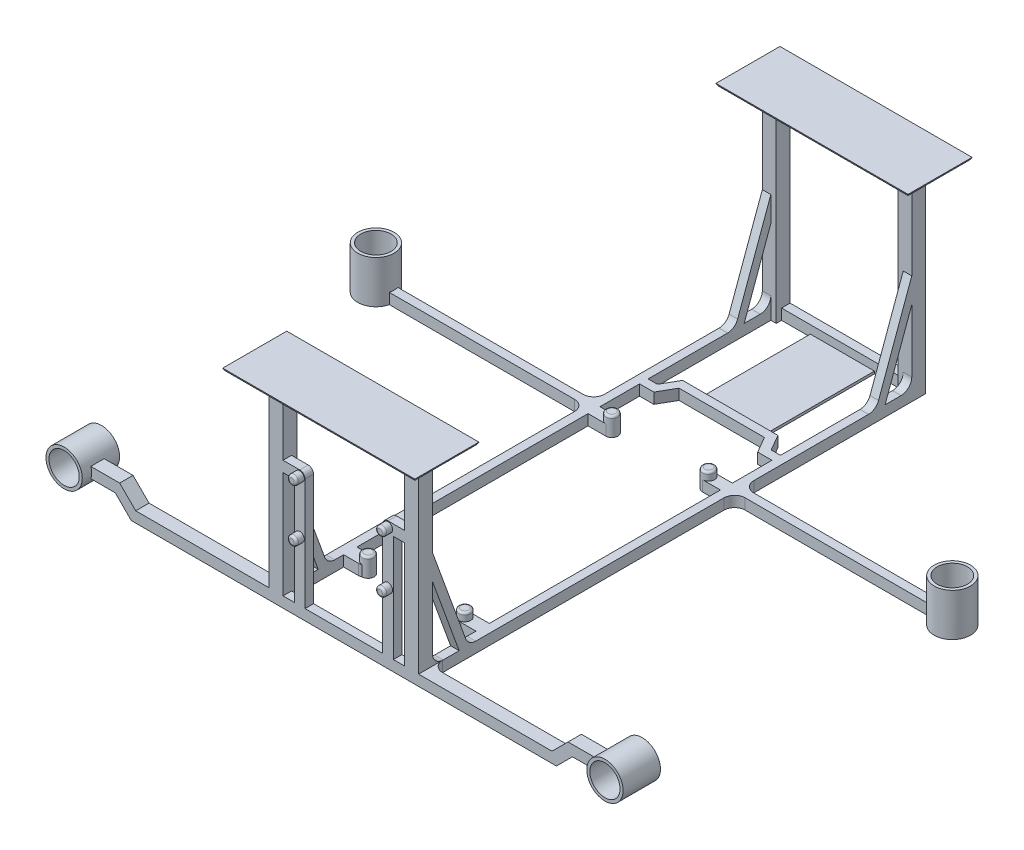
SolidWorks part; units mm, degrees
ref_plane "Front Plane" through (0, 0, 0) normal (0, 0, 1) x (1, 0, 0)
ref_plane "Top Plane" through (0, 0, 0) normal (0, 1, 0) x (1, 0, 0)
ref_plane "Right Plane" through (0, 0, 0) normal (1, 0, 0) x (0, 0, -1)
sketch "Sketch1" plane through (0, 0, 0) normal (0, 1, 0) x (1, 0, 0)
  line L6 (17.78, -60.325) -> (-17.78, -60.325)
  line L14 (17.78, -60.325) -> (17.78, 60.325)
  line L17 (17.78, 60.325) -> (-17.78, 60.325)
  line L19 (-17.78, -60.325) -> (-17.78, 60.325)
  line L20 (17.78, -60.325) -> (-17.78, 60.325) construction
  line L21 (17.78, 60.325) -> (-17.78, -60.325) construction
  line L22 (-15.748, -57.023) -> (-15.748, -44.6405)
  line L23 (14.478, -58.293) -> (-14.478, -58.293)
  line L24 (15.748, -57.023) -> (15.748, -44.6405)
  line L33 (-11.5, -43.053) -> (11.5, -43.053) construction
  line L34 (-11.5, -43.053) -> (-11.5, 14.947) construction
  line L35 (-11.5, 14.947) -> (11.5, 14.947) construction
  line L36 (11.5, -43.053) -> (11.5, 14.947) construction
  line L37 (0, -43.053) -> (0, -58.293) construction
  line L39 (-15.748, 25.781) -> (-12.3597, 25.781)
  line L43 (-15.748, -41.4655) -> (-11.5, -41.4655)
  line L44 (-15.748, -44.6405) -> (-11.5, -44.6405)
  line L45 (-11.5, -41.4655) -> (-11.5, -44.6405)
  line L46 (15.748, -41.4655) -> (11.5, -41.4655)
  line L47 (11.5, -41.4655) -> (11.5, -44.6405)
  line L48 (11.5, -44.6405) -> (15.748, -44.6405)
  line L52 (-15.748, -41.4655) -> (-15.748, 13.5246)
  line L53 (-15.748, -58.293) -> (-15.748, 58.293) construction
  line L54 (15.748, -41.4655) -> (15.748, 13.5246)
  line L55 (15.748, -58.293) -> (15.748, 58.293) construction
  line L58 (-15.748, 27.813) -> (-13.5329, 27.813)
  line L68 (1.016, 33.7192) -> (-1.016, 33.7192) construction
  line L70 (1.016, 33.7192) -> (-1.016, 33.7192) construction
  line L73 (0, 33.7192) -> (0, 29.591) construction
  line L75 (14.478, 58.293) -> (10.668, 58.293)
  line L76 (15.748, 58.293) -> (-15.748, 58.293) construction
  line L82 (-15.748, 27.813) -> (-15.748, 57.023)
  line L83 (15.748, 27.813) -> (15.748, 57.023)
  line L87 (-15.748, 57.023) -> (-14.478, 57.023)
  line L88 (-14.478, 58.293) -> (-14.478, 57.023)
  line L92 (15.748, 57.023) -> (14.478, 57.023)
  line L93 (14.478, 58.293) -> (14.478, 57.023)
  line L97 (-15.748, -57.023) -> (-14.478, -57.023)
  line L98 (-14.478, -58.293) -> (-14.478, -57.023)
  line L99 (15.748, -58.293) -> (-15.748, -58.293) construction
  line L102 (15.748, -57.023) -> (14.478, -57.023)
  line L103 (14.478, -58.293) -> (14.478, -57.023)
  line L104 (-12.3597, 25.781) -> (-10.16, 29.591)
  line L105 (-10.16, 29.591) -> (10.16, 29.591)
  line L106 (10.16, 29.591) -> (12.3597, 25.781)
  line L108 (-13.5329, 27.813) -> (-10.668, 32.7751)
  line L109 (-8.636, 31.623) -> (-1.016, 31.623)
  line L110 (10.668, 32.7751) -> (13.5329, 27.813)
  line L112 (-8.636, 31.623) -> (-8.636, 58.293)
  line L114 (-10.668, 32.7751) -> (-10.668, 58.293)
  line L115 (10.668, 32.7751) -> (10.668, 58.293)
  line L116 (8.636, 31.623) -> (8.636, 58.293)
  line L117 (-1.016, 58.293) -> (-1.016, 31.623)
  line L118 (1.016, 31.623) -> (1.016, 58.293)
  line L119 (-1.016, 58.293) -> (-8.636, 58.293)
  line L120 (8.636, 58.293) -> (1.016, 58.293)
  line L121 (-10.668, 58.293) -> (-14.478, 58.293)
  line L122 (1.016, 31.623) -> (8.636, 31.623)
  line L124 (13.5329, 27.813) -> (15.748, 27.813)
  line L125 (-10.668, 35.6338) -> (-8.636, 35.6338) construction
  line L126 (8.636, 39.2988) -> (10.668, 39.2988) construction
  line L138 (12.3597, 25.781) -> (15.748, 25.781)
  line L140 (-11.5, 16.3694) -> (-15.748, 16.3694)
  line L142 (-11.5, 13.5246) -> (-15.748, 13.5246)
  line L144 (11.5, 16.3694) -> (15.748, 16.3694)
  line L146 (11.5, 13.5246) -> (15.748, 13.5246)
  line L148 (11.5, 16.3694) -> (11.5, 13.5246)
  line L149 (-11.5, 16.3694) -> (-11.5, 13.5246)
  line L150 (-15.748, 16.3694) -> (-15.748, 25.781)
  line L151 (15.748, 16.3694) -> (15.748, 25.781)
  circle A0 centre (-11.5, -43.053) radius 1.4224 construction
  circle A1 centre (11.5, -43.053) radius 1.4224 construction
  circle A3 centre (-11.5, 14.947) radius 1.4224 construction
  circle A4 centre (11.5, 14.947) radius 1.4224 construction
  point P0 (0, 0)
  point P50 (0, 33.7192)
  point P54 (0, 33.7192)
  point P85 (0, 29.591)
  dimension "D5" = 2.8448
  dimension "D14" = 2.032
  dimension "D20" = 2.032
  dimension "D2" = 120.65
  dimension "D3" = 2.032
  dimension "D4" = 23
  dimension "D6" = 15.24
  dimension "D7" = 58
  dimension "D8" = 2.032
  dimension "D9" = 60
  dimension "D11" = 3.175
  dimension "D13" = 3.175
  dimension "D15" = 30.48
  dimension "D16" = 7.62
  dimension "D17" = 2.032
  dimension "D18" = 20.32
  dimension "D19" = 1.27
  dimension "D21" = 2.032
  dimension "D22" = 3.81
  dimension "D1" = 35.56
extrude "Boss-Extrude1" add sketch "Sketch1" along normal blind 2.54
sketch "Sketch5" plane through (0, 2.54, 0) normal (0, 1, 0) x (1, 0, 0)
  line L1 (-17.78, 60.325) -> (-14.478, 60.325)
  line L2 (-17.78, 60.325) -> (-17.78, 57.023)
  line L3 (-17.78, 57.023) -> (-14.478, 57.023)
  line L4 (-14.478, 60.325) -> (-14.478, 57.023)
  line L5 (17.78, 60.325) -> (14.478, 60.325)
  line L6 (17.78, 60.325) -> (17.78, 57.023)
  line L7 (17.78, 57.023) -> (14.478, 57.023)
  line L8 (14.478, 60.325) -> (14.478, 57.023)
  line L9 (17.78, -60.325) -> (14.478, -60.325)
  line L10 (17.78, -60.325) -> (17.78, -57.023)
  line L11 (17.78, -57.023) -> (14.478, -57.023)
  line L12 (14.478, -60.325) -> (14.478, -57.023)
  line L13 (-14.478, -57.023) -> (-17.78, -57.023)
  line L14 (-14.478, -57.023) -> (-14.478, -60.325)
  line L15 (-14.478, -60.325) -> (-17.78, -60.325)
  line L16 (-17.78, -57.023) -> (-17.78, -60.325)
  line L17 (-14.478, 58.293) -> (-14.478, 57.023) construction
extrude "Boss-Extrude3" add sketch "Sketch5" along normal blind 44.45
sketch "Sketch38" plane through (0, 46.99, 0) normal (0, 1, 0) x (1, 0, 0)
  line L0 (0, 0) -> (0, 60.325) construction
  line L5 (14.478, 60.325) -> (-14.478, 60.325) construction
  line L6 (-17.78, 58.674) -> (17.78, 58.674) construction
  line L11 (0, 0) -> (-17.78, 0) construction
  line L12 (17.78, -60.325) -> (17.78, -57.023)
  line L13 (17.78, -57.023) -> (14.478, -57.023)
  line L22 (14.478, -57.023) -> (14.478, -60.325)
  line L23 (14.478, -60.325) -> (17.78, -60.325)
  line L33 (17.78, -57.023) -> (14.478, -57.023) construction
  line L34 (14.478, -57.023) -> (14.478, -60.325) construction
  line L36 (14.478, -60.325) -> (17.78, -60.325) construction
  line L37 (-14.478, -60.325) -> (-14.478, -57.023)
  line L38 (-14.478, -57.023) -> (-17.78, -57.023)
  line L39 (-17.78, -57.023) -> (-17.78, -60.325)
  line L51 (-17.78, -57.023) -> (-17.78, -60.325) construction
  line L52 (-14.478, -60.325) -> (-14.478, -57.023) construction
  line L53 (-14.478, -57.023) -> (-17.78, -57.023) construction
  line L56 (17.78, 57.023) -> (17.78, 60.325)
  line L57 (17.78, 60.325) -> (14.478, 60.325)
  line L58 (14.478, 60.325) -> (14.478, 57.023)
  line L59 (14.478, 57.023) -> (17.78, 57.023)
  line L60 (17.78, 57.023) -> (17.78, 60.325) construction
  line L62 (14.478, 60.325) -> (14.478, 57.023) construction
  line L63 (14.478, 57.023) -> (17.78, 57.023) construction
  line L64 (-17.78, 60.325) -> (-17.78, 57.023)
  line L65 (-17.78, 57.023) -> (-14.478, 57.023)
  line L66 (-14.478, 57.023) -> (-14.478, 60.325)
  line L67 (-14.478, 60.325) -> (-17.78, 60.325)
  line L68 (-17.78, 60.325) -> (-17.78, 57.023) construction
  line L69 (-17.78, 57.023) -> (-14.478, 57.023) construction
  line L70 (-14.478, 57.023) -> (-14.478, 60.325) construction
  line L71 (-14.478, 60.325) -> (-17.78, 60.325) construction
  line L72 (22.86, 51.054) -> (-22.86, 51.054)
  line L73 (22.86, 51.054) -> (22.86, 66.294)
  line L74 (22.86, 66.294) -> (-22.86, 66.294)
  line L75 (-22.86, 51.054) -> (-22.86, 66.294)
  line L76 (22.86, 51.054) -> (-22.86, 66.294) construction
  line L77 (22.86, 66.294) -> (-22.86, 51.054) construction
  line L78 (-17.78, 57.023) -> (-17.78, -57.023) construction
  line L79 (22.86, -66.294) -> (-22.86, -51.054) construction
  line L80 (22.86, -51.054) -> (-22.86, -66.294) construction
  line L81 (-14.478, -60.325) -> (-17.78, -60.325) construction
  line L82 (-14.478, -57.023) -> (-14.478, -60.325) construction
  line L83 (-17.78, -57.023) -> (-14.478, -57.023) construction
  line L84 (-17.78, -60.325) -> (-17.78, -57.023) construction
  line L85 (14.478, -57.023) -> (17.78, -57.023) construction
  line L86 (14.478, -60.325) -> (14.478, -57.023) construction
  line L87 (17.78, -60.325) -> (14.478, -60.325) construction
  line L88 (17.78, -57.023) -> (17.78, -60.325) construction
  line L89 (-17.78, -58.674) -> (17.78, -58.674) construction
  line L90 (-22.86, -51.054) -> (-22.86, -66.294)
  line L91 (22.86, -66.294) -> (-22.86, -66.294)
  line L92 (22.86, -51.054) -> (22.86, -66.294)
  line L93 (22.86, -51.054) -> (-22.86, -51.054)
  line L98 (17.78, -60.325) -> (17.78, -57.023) construction
  line L99 (-17.78, -60.325) -> (-14.478, -60.325)
  line L100 (-17.78, -60.325) -> (-14.478, -60.325) construction
  line L101 (17.78, 60.325) -> (14.478, 60.325) construction
  point P23 (0, 58.674)
  point P38 (0, -58.674)
  dimension "D1" = 0
  dimension "D5" = 15.24
  dimension "D6" = 5.08
  dimension "D2" = 0
  dimension "D3" = 0
  dimension "D4" = 0
extrude "Boss-Extrude22" add sketch "Sketch38" along normal blind 1.27
fillet "Fillet17" radius 1.905 24 edges at (-14.478, 46.99, -58.674) (-16.129, 46.99, -57.023) (-17.78, 46.99, -58.674) (-16.129, 46.99, -60.325) (14.478, 46.99, -58.674) (16.129, 46.99, -60.325) (17.78, 46.99, -58.674) (16.129, 46.99, -57.023) (0, 46.99, -51.054) (22.86, 46.99, -58.674) (0, 46.99, -66.294) (-22.86, 46.99, -58.674) (-16.129, 46.99, 57.023) (-14.478, 46.99, 58.674) (-16.129, 46.99, 60.325) (-17.78, 46.99, 58.674) (0, 46.99, 51.054) (-22.86, 46.99, 58.674) (0, 46.99, 66.294) (22.86, 46.99, 58.674) (14.478, 46.99, 58.674) (16.129, 46.99, 57.023) (17.78, 46.99, 58.674) (16.129, 46.99, 60.325)
sketch "Sketch19" plane through (-17.78, 0, 0) normal (-1, 0, 0) x (0, 0, 1)
  line L0 (-57.023, 19.9865) -> (-50.673, 2.54)
  line L1 (-57.023, 45.085) -> (-57.023, 2.54) construction
  line L2 (-57.023, 2.54) -> (57.023, 2.54) construction
  line L3 (-50.673, 2.54) -> (-48.5106, 2.54)
  line L4 (-48.5106, 2.54) -> (-57.023, 25.9277)
  line L5 (-57.023, 25.9277) -> (-57.023, 19.9865)
  line L6 (0, 0) -> (0, 23.6424) construction
  line L7 (-60.325, 0) -> (60.325, 0) construction
  line L8 (50.673, 2.54) -> (48.5106, 2.54)
  line L9 (57.023, 25.9277) -> (57.023, 19.9865)
  line L10 (57.023, 19.9865) -> (50.673, 2.54)
  line L11 (48.5106, 2.54) -> (57.023, 25.9277)
  dimension "D1" = 2.032
  dimension "D2" = 70
  dimension "D3" = 6.35
extrude "Boss-Extrude11" add sketch "Sketch19" against normal blind 2.032
mirror "Mirror11" about plane through (0, 0, 0) normal (1, 0, 0) of "Boss-Extrude11"
fillet "Fillet7" radius 2.54 8 edges at (16.764, 2.54, -48.5106) (-16.764, 2.54, -48.5106) (-16.764, 2.54, 48.5106) (16.764, 2.54, 48.5106) (16.764, 2.54, 57.023) (-16.764, 2.54, -57.023) (16.764, 2.54, -57.023) (-16.764, 2.54, 57.023) tangent propagation no
sketch "Sketch12" plane through (0, 0, 0) normal (0, 1, 0) x (1, 0, 0)
  line L0 (-17.78, 16.891) -> (-64.3832, 16.891)
  line L1 (-17.78, 57.023) -> (-17.78, -57.023) construction
  line L2 (-17.78, 14.859) -> (-64.3832, 14.859)
  line L3 (-17.78, 14.859) -> (-17.78, 16.891)
  line L7 (-17.78, 46.7321) -> (-17.78, -46.7321) construction
  line L8 (-14.478, -60.325) -> (14.478, -60.325) construction
  line L9 (-17.78, 15.875) -> (-68.58, 15.875) construction
  arc A1 (-64.3832, 16.891) -> (-64.3832, 14.859) centre (-68.58, 15.875) ccw
  point P9 (-17.78, 15.875)
  dimension "D3" = 50.8
  dimension "D2" = 4.318
  dimension "D1" = 2.032
  dimension "D7" = 76.2
extrude "Boss-Extrude26" add sketch "Sketch12" along normal blind 2.54 contours L2 A1 L0 region at (-51.5768, 0, -15.875)
sketch "Sketch47" plane through (0, 2.54, 0) normal (0, 1, 0) x (1, 0, 0)
  circle A1 centre (-68.58, 15.875) radius 4.318
  circle A2 centre (-68.58, 15.875) radius 3.6
  arc A3 (-64.3832, 16.891) -> (-64.3832, 14.859) centre (-68.58, 15.875) ccw construction
  dimension "D1" = 7.2
extrude "Boss-Extrude28" add sketch "Sketch47" along normal blind 7.62
sketch "Sketch48" plane through (0, 2.54, 0) normal (0, 1, 0) x (1, 0, 0)
  line L0 (-71.3063, 18.2261) -> (-70.0363, 18.2261)
  line L1 (-70.0363, 18.2261) -> (-70.0363, 13.7619)
  line L2 (-70.0363, 13.7619) -> (-71.4946, 13.7619)
  line L3 (-65.8537, 18.2261) -> (-67.506, 18.2261)
  line L4 (-67.506, 18.2261) -> (-67.506, 13.3162)
  line L5 (-67.506, 13.3162) -> (-66.0477, 13.3162)
  line L6 (-67.506, 15.7711) -> (-70.0363, 15.994) construction
  arc A0 (-66.0477, 13.3162) -> (-65.8537, 18.2261) centre (-68.7712, 15.8826) ccw
  arc A1 (-66.0477, 13.3162) -> (-65.8537, 18.2261) centre (-68.58, 15.875) ccw
  circle A3 centre (-68.58, 15.875) radius 3.6
  arc A4 (-71.3063, 18.2261) -> (-71.4946, 13.7619) centre (-68.58, 15.875) ccw
  point P14 (-68.7712, 15.8826)
  circle M8 centre (-68.58, 15.875) radius 3.6
  dimension "D2" = 2.54
  dimension "D3" = 1.27
  dimension "D1" = 0
extrude "Cut-Extrude1" cut sketch "Sketch48" against normal through all contours L4 L5 L3 M8 | L2 L1 L0 M8 region at (-70.998, 2.54, -15.9607) region at (-66.3962, 2.54, -15.8032)
sketch "Sketch7" plane through (0, 0, 60.325) normal (0, 0, 1) x (1, 0, 0)
  line L0 (-14.478, 2.54) -> (-49.53, 2.54)
  line L1 (-49.53, 2.54) -> (-53.34, 6.35)
  line L3 (-54.3921, 3.81) -> (-50.5821, 0)
  line L4 (-50.5821, 0) -> (-14.478, 0)
  line L5 (-51.3261, 0.7439) -> (-49.53, 2.54) construction
  line L7 (-54.3921, 3.81) -> (-54.3921, 6.35) construction
  line L8 (-54.3921, 3.81) -> (-60.7421, 3.81)
  line L9 (-60.7421, 3.81) -> (-60.7421, 6.35)
  line L10 (-60.7421, 6.35) -> (-53.34, 6.35)
  line L11 (-17.78, 0) -> (17.78, 0) construction
  line L12 (-14.478, 2.54) -> (-14.478, 0)
  line L13 (-17.78, 45.085) -> (-17.78, 0) construction
  point P10 (-54.3921, 5.08)
  line M14 (-17.78, 45.085) -> (-17.78, 0)
  dimension "D1" = 5.08
  dimension "D2" = 31.75
  dimension "D3" = 45
  dimension ".75" = 6.35
  dimension "D5" = 2.54
extrude "Boss-Extrude4" add sketch "Sketch7" against normal blind 3.175 contours L10 L9 L8 L3 L4 L0 L1 M14 region at (-39.711, 2.0886, 60.325)
ref_plane "Plane2" through (0, 0, 58.7375) normal (0, 0, 1) x (1, 0, 0)
sketch "Sketch50" plane through (0, 0, 58.7375) normal (0, 0, 1) x (1, 0, 0)
  line L0 (-60.7421, 3.81) -> (-60.7421, 6.35) construction
  line L1 (-64.3421, 5.08) -> (-60.7421, 5.08) construction
  circle A0 centre (-64.3421, 5.08) radius 3.6
  circle A1 centre (-64.3421, 5.08) radius 4.318
  dimension "D1" = 8.636
  dimension "D2" = 7.2
extrude "Boss-Extrude29" add sketch "Sketch50" along normal blind 3.81 and the other way blind 3.81
sketch "Sketch51" plane through (0, 0, 54.9275) normal (0, 0, -1) x (-1, 0, 0)
  line L0 (61.8021, 7.6312) -> (63.0721, 7.6312)
  line L1 (63.0721, 7.6312) -> (63.0721, 2.5288)
  line L2 (63.0721, 2.5288) -> (61.8021, 2.5288)
  line L3 (66.8821, 7.6312) -> (65.6121, 7.6312)
  line L4 (65.6121, 7.6312) -> (65.6121, 2.5288)
  line L5 (65.6121, 2.5288) -> (66.8821, 2.5288)
  line L6 (63.0721, 5.08) -> (65.6121, 5.08) construction
  circle A1 centre (64.3421, 5.08) radius 3.6 construction
  circle A2 centre (64.3421, 5.08) radius 4.318
  circle A3 centre (64.3421, 5.08) radius 4.318
  arc A4 (61.8021, 7.6312) -> (61.8021, 2.5288) centre (64.3421, 5.08) ccw
  arc A5 (66.8821, 2.5288) -> (66.8821, 7.6312) centre (64.3421, 5.08) ccw
  point P17 (64.3421, 5.08)
  dimension "D2" = 2.54
  dimension "D3" = 1.27
  dimension "D1" = 0
extrude "Boss-Extrude30" add sketch "Sketch51" along normal blind 1.27
ref_plane "Plane1" through (0, 0, 0) normal (-1, 0, 0) x (0, 0, 1)
mirror "Mirror10" about plane through (0, 0, 0) normal (1, 0, 0) of "Boss-Extrude30", "Boss-Extrude29", "Cut-Extrude1", "Boss-Extrude28", "Boss-Extrude4", "Boss-Extrude26"
fillet "Fillet23" radius 2.54 6 edges at (-17.78, 1.27, -16.891) (-17.78, 1.27, -14.859) (17.78, 1.27, -16.891) (17.78, 1.27, -14.859) (17.78, 1.27, 57.15) (-17.78, 1.27, 57.15)
sketch "Sketch41" plane through (0, 2.54, 0) normal (0, 1, 0) x (1, 0, 0)
  circle A0 centre (11.5, -43.053) radius 1.4224 construction
  circle A1 centre (-11.5, -43.053) radius 1.4224 construction
  circle A2 centre (-11.5, 14.947) radius 1.4224 construction
  circle A3 centre (11.5, 14.947) radius 1.4224 construction
  circle A4 centre (11.5, -43.053) radius 1.4224
  circle A5 centre (-11.5, -43.053) radius 1.4224
  circle A6 centre (-11.5, 14.947) radius 1.4224
  circle A7 centre (11.5, 14.947) radius 1.4224
extrude "Boss-Extrude23" add sketch "Sketch41" along normal blind 1.905 and the other way up to surface other way up to face at (66.4987, 0, -15.762)
fillet "Fillet18" radius 0.508 4 edges at (11.5, 4.445, 44.4754) (-11.5, 4.445, 44.4754) (11.5, 4.445, -13.5246) (-11.5, 4.445, -13.5246)
fillet "Fillet19" radius 1.524 4 edges at (11.5, 1.27, 44.6405) (11.5, 1.27, 41.4655) (-11.5, 1.27, 44.6405) (-11.5, 1.27, 41.4655)
sketch "Sketch42" plane through (0, 0, 60.325) normal (0, 0, 1) x (1, 0, 0)
  line L0 (-9.23, 2.54) -> (-9.23, 30.48)
  line L1 (-14.478, 2.54) -> (14.478, 2.54) construction
  line L2 (-11.77, 27.94) -> (-14.478, 27.94)
  line L3 (9.23, 2.54) -> (9.23, 30.48)
  line L4 (0, 29.21) -> (0, 0) construction
  line L5 (-14.478, 45.085) -> (-14.478, 2.54) construction
  line L6 (-11.77, 2.54) -> (-11.77, 27.94)
  line L7 (9.23, 30.48) -> (14.478, 30.48)
  line L8 (11.77, 27.94) -> (11.77, 2.54)
  line L9 (-11.77, 16.71) -> (-9.23, 16.71) construction
  line L10 (9.23, 16.71) -> (11.77, 16.71) construction
  line L12 (11.77, 27.94) -> (14.478, 27.94)
  line L13 (-9.23, 30.48) -> (-14.478, 30.48)
  line L14 (-10.5, 29.21) -> (10.5, 29.21) construction
  line L15 (-11.77, 27.94) -> (-9.23, 30.48) construction
  line L17 (11.77, 27.94) -> (9.23, 30.48) construction
  line L18 (-50.5821, 0) -> (50.5821, 0) construction
  line L19 (-14.478, 30.48) -> (-14.478, 27.94)
  line L20 (14.478, 30.48) -> (14.478, 27.94)
  line L21 (9.23, 2.54) -> (11.77, 2.54)
  line L22 (-9.23, 2.54) -> (-11.77, 2.54)
  line L23 (14.478, 45.085) -> (14.478, 2.54) construction
  circle A0 centre (-10.5, 16.71) radius 1.1 construction
  circle A1 centre (-10.5, 29.21) radius 1.1 construction
  circle A2 centre (10.5, 29.21) radius 1.1 construction
  circle A3 centre (10.5, 16.71) radius 1.1 construction
  line M19 (14.478, 2.54) -> (-14.478, 2.54)
  dimension "D4" = 2.2
  dimension "D5" = 2.54
  dimension "D2" = 2.54
  dimension "D3" = 12.5
  dimension "D1" = 2.54
  dimension "D6" = 25.4
  dimension "D7" = 21
extrude "Boss-Extrude25" add sketch "Sketch42" against normal up to surface (2.032 mm away) contours L8 L12 L7 L3 M19 | L13 L19 L2 L6 L22 L0 region at (10.7319, 17.6321, 60.325) up to face at (0, 1.27, 58.293)
sketch "Sketch43" plane through (0, 0, 60.325) normal (0, 0, 1) x (1, 0, 0)
  circle A0 centre (10.5, 16.71) radius 1.1 construction
  circle A1 centre (10.5, 29.21) radius 1.1 construction
  circle A2 centre (-10.5, 16.71) radius 1.1 construction
  circle A3 centre (-10.5, 29.21) radius 1.1 construction
  circle A4 centre (10.5, 16.71) radius 1.1
  circle A5 centre (10.5, 29.21) radius 1.1
  circle A6 centre (-10.5, 16.71) radius 1.1
  circle A7 centre (-10.5, 29.21) radius 1.1
extrude "Boss-Extrude24" add sketch "Sketch43" along normal blind 1.905
fillet "Fillet20" radius 0.508 4 edges at (11.6, 29.21, 62.23) (11.6, 16.71, 62.23) (-9.4, 16.71, 62.23) (-9.4, 29.21, 62.23)
fillet "Fillet22" radius 1.27 2 edges at (9.23, 30.48, 59.309) (-9.23, 30.48, 59.309)
sketch "Sketch44" plane through (0, 0, 60.325) normal (0, 0, 1) x (1, 0, 0)
  circle A0 centre (-64.3421, 5.08) radius 37.5
  circle A1 centre (64.3421, 5.08) radius 37.5
  dimension "75mm" = 75
sketch "Sketch45" plane through (0, 2.54, 0) normal (0, 1, 0) x (1, 0, 0)
  circle A0 centre (-68.58, 15.875) radius 37.5
  circle A1 centre (68.58, 15.875) radius 37.5
  dimension "D2" = 75
sketch "Sketch52" plane through (0, 2.54, 0) normal (0, 1, 0) x (1, 0, 0)
  line L0 (1.016, 31.623) -> (8.636, 31.623) construction
  line L1 (-11.3332, 58.293) -> (11.3332, 58.293)
  line L2 (-11.3332, 58.293) -> (-11.3332, 31.623)
  line L3 (-11.3332, 31.623) -> (11.3332, 31.623)
  line L4 (11.3332, 58.293) -> (11.3332, 31.623)
  line L6 (-13.5329, 27.813) -> (-10.668, 32.7751) construction
  line L7 (10.668, 32.7751) -> (13.5329, 27.813) construction
extrude "Cut-Extrude2" cut sketch "Sketch52" against normal through all
sketch "Sketch53" plane through (0, 0, 0) normal (0, -1, 0) x (1, 0, 0)
  line L0 (-11.3332, -31.623) -> (11.3332, -31.623) construction
  line L1 (-7.62, -31.623) -> (7.62, -31.623)
  line L2 (-7.62, -31.623) -> (-7.62, -58.293)
  line L3 (-7.62, -58.293) -> (7.62, -58.293)
  line L4 (7.62, -31.623) -> (7.62, -58.293)
  line L6 (0, -31.623) -> (0, -29.591) construction
  line L7 (10.16, -29.591) -> (-10.16, -29.591) construction
  line L8 (14.478, -58.293) -> (-14.478, -58.293) construction
  dimension "D1" = 15.24
extrude "Boss-Extrude31" add sketch "Sketch53" against normal blind 0.6
